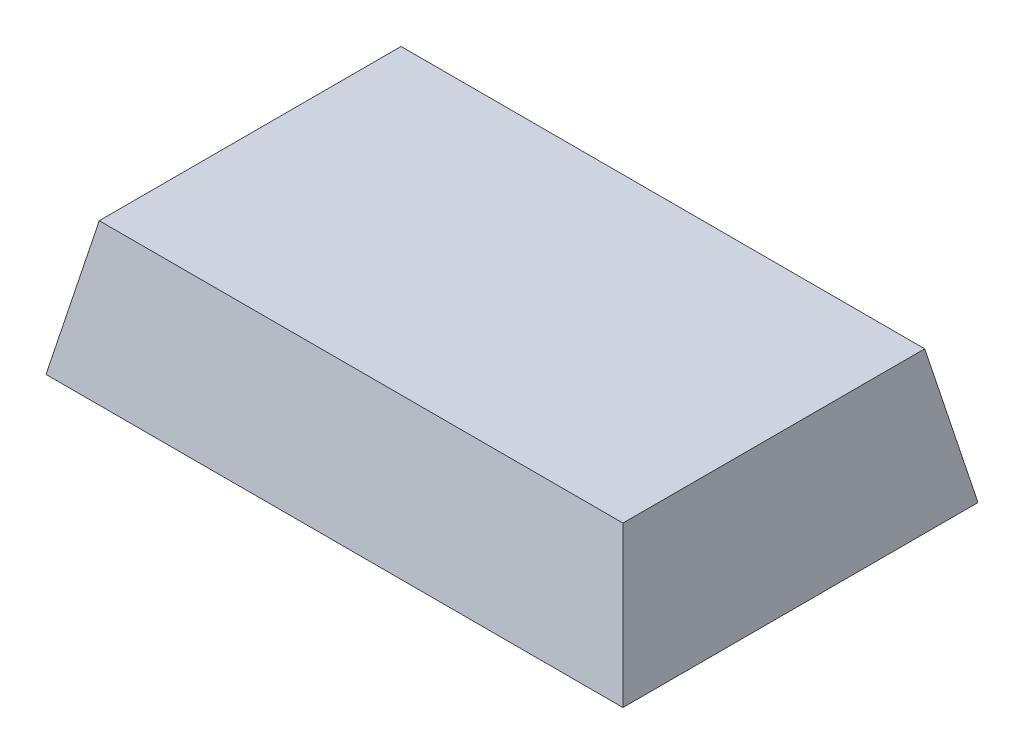
SolidWorks part; units mm, degrees
ref_plane "Front Plane" through (0, 0, 0) normal (0, 0, 1) x (1, 0, 0)
ref_plane "Top Plane" through (0, 0, 0) normal (0, 1, 0) x (1, 0, 0)
ref_plane "Right Plane" through (0, 0, 0) normal (1, 0, 0) x (0, 0, -1)
sketch "Sketch1" plane through (0, 0, 0) normal (0, 1, 0) x (1, 0, 0)
  line L1 (0, 0) -> (13, 0)
  line L2 (0, 0) -> (0, 8)
  line L3 (0, 8) -> (13, 8)
  line L4 (13, 0) -> (13, 8)
  dimension "D1" = 8
  dimension "D2" = 13
extrude "Boss-Extrude1" add sketch "Sketch1" along normal blind 3
sketch "Sketch2" plane through (0, 0, 0) normal (0, 0, 1) x (1, 0, 0)
  line L0 (0, 0) -> (0.6, 3)
  line L1 (0, 3) -> (13, 3) construction
  line L2 (0.6, 3) -> (0, 3)
  line L3 (0, 3) -> (0, 0)
  line L4 (13, 0) -> (12.4, 3)
  line L5 (12.4, 3) -> (13, 3)
  line L6 (13, 3) -> (13, 0)
  dimension "D1" = 0.6
  dimension "D2" = 0.6
extrude "Cut-Extrude1" cut sketch "Sketch2" against normal through all both and the other way through all
sketch "Sketch3" plane through (0, 0, 0) normal (1, 0, 0) x (0, 0, -1)
  line L0 (0, 0) -> (0.6, 3)
  line L1 (8, 3) -> (0, 3) construction
  line L2 (0.6, 3) -> (0, 3)
  line L3 (0, 3) -> (0, 0)
  line L4 (8, 3) -> (7.4, 3)
  line L5 (7.4, 3) -> (8, 0)
  line L6 (8, 3) -> (8, 0)
  dimension "D1" = 0.6
  dimension "D2" = 0.6
extrude "Cut-Extrude2" cut sketch "Sketch3" along normal through all both and the other way through all
sketch "Sketch4" plane through (0, 0, 0) normal (0, -1, 0) x (1, 0, 0)
  line L1 (6.5, 0) -> (6.5, -8) construction
  line L2 (13, -8) -> (0, -8) construction
  line L3 (0, 0) -> (13, 0) construction
  circle A0 centre (6.5, -3.75) radius 1.8
  dimension "D1" = 3.6
  dimension "D2" = 0
  dimension "D3" = 3.75
extrude "Cut-Extrude3" cut sketch "Sketch4" against normal blind 0.8
sketch "Sketch5" plane through (0, 0, 0) normal (0, -1, 0) x (1, 0, 0)
  line L5 (0, 0) -> (13, 0) construction
  line L6 (2.5, -8) -> (10.5, -8)
  line L7 (2.5, -8) -> (2.5, -7)
  line L8 (2.5, -7) -> (10.5, -7)
  line L9 (10.5, -8) -> (10.5, -7)
  point P2 (6.5, 0)
  dimension "D1" = 1
  dimension "D2" = 4
  dimension "D3" = 4
extrude "Boss-Extrude2" add sketch "Sketch5" along normal blind 2
fillet "Fillet1" radius 4 2 edges at (10.5, -2, -7.5) (2.5, -2, -7.5)
